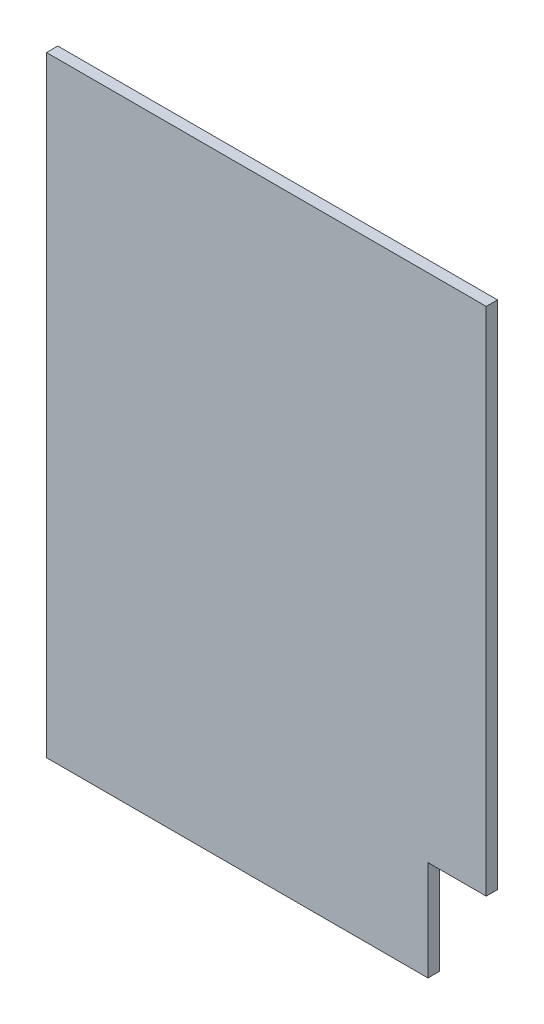
SolidWorks part; units mm, degrees
ref_plane "Front Plane" through (0, 0, 0) normal (0, 0, 1) x (1, 0, 0)
ref_plane "Top Plane" through (0, 0, 0) normal (0, 1, 0) x (1, 0, 0)
ref_plane "Right Plane" through (0, 0, 0) normal (1, 0, 0) x (0, 0, -1)
sketch "Sketch1" plane through (0, 0, 0) normal (0, 0, 1) x (1, 0, 0)
  line L1 (0, 0) -> (1015, 0)
  line L2 (0, 0) -> (0, 1625)
  line L3 (0, 1625) -> (1170, 1625)
  line L4 (1170, 266) -> (1170, 1625)
  line L5 (1170, 266) -> (1015, 266)
  line L8 (1015, 266) -> (1015, 0)
  dimension "D1" = 1170
  dimension "D2" = 1625
  dimension "D3" = 155
  dimension "D4" = 266
extrude "Boss-Extrude1" add sketch "Sketch1" along normal blind 30
